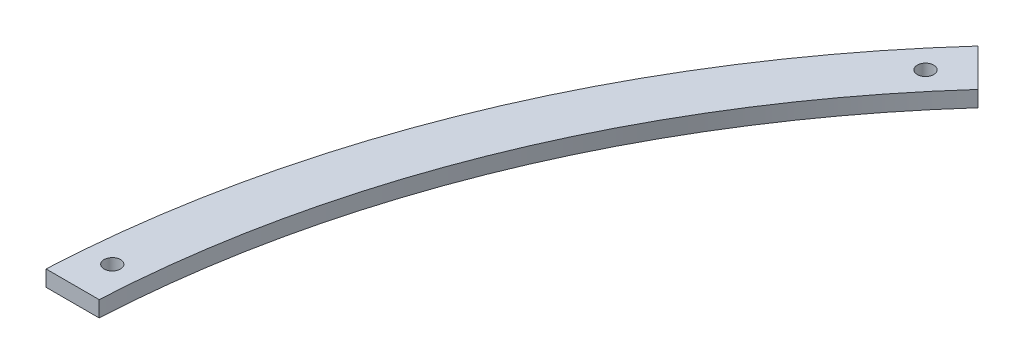
SolidWorks part; units mm, degrees
ref_plane "Front Plane" through (0, 0, 0) normal (0, 0, 1) x (1, 0, 0)
ref_plane "Top Plane" through (0, 0, 0) normal (0, 1, 0) x (1, 0, 0)
ref_plane "Right Plane" through (0, 0, 0) normal (1, 0, 0) x (0, 0, -1)
sketch "Sketch1" plane through (0, 0, 0) normal (0, 1, 0) x (1, 0, 0)
  line L1 (0, 200) -> (0, -200) construction
  line L6 (-200, 0) -> (200, 0) construction
  line L7 (-10, 199.7498) -> (-10, -199.7498) construction
  line L12 (-10, 199.7498) -> (-10, 189.7367)
  line L13 (-199.7498, 10) -> (199.7498, 10) construction
  line L14 (-199.7498, 10) -> (-189.7367, 10)
  line L15 (-141.4214, 141.4214) -> (141.4214, -141.4214) construction
  line L16 (-148.3155, 134.1734) -> (134.1734, -148.3155)
  arc A3 (-10, 199.7498) -> (-199.7498, 10) centre (0, 0) ccw
  arc A4 (-10, 189.7367) -> (-189.7367, 10) centre (0, 0) ccw
  arc A5 (-190, 0) -> (-189.7367, 10) centre (0, 0) ccw construction
  arc A6 (-200, 0) -> (-199.7498, 10) centre (0, 0) ccw construction
  circle A7 centre (0, 0) radius 195 construction
  dimension "D1" = 190
  dimension "D2" = 200
  dimension "D4" = 10
  dimension "D5" = 5
  dimension "D3" = 10
  dimension "D6" = 10
sketch "Sketch14" [suppressed] plane through (0, 0, 0) normal (0, 1, 0) x (1, 0, 0)
  line L0 (-200, 10) -> (200, 10) construction
  line L1 (-10, 200) -> (-10, -200) construction
  line L2 (-200, 10) -> (-189.7367, 10)
  line L3 (-10, 200) -> (-10, 189.7367)
  circle A0 centre (0, 0) radius 200 construction
  circle A1 centre (0, 0) radius 190 construction
  arc A2 (-10, 199.7498) -> (-199.7498, 10) centre (0, 0) ccw
  arc A3 (-10, 189.7367) -> (-189.7367, 10) centre (0, 0) ccw
sketch "roll" plane through (0, 0, 0) normal (0, 1, 0) x (1, 0, 0)
  line L0 (0, -195) -> (0, 195) construction
  dimension "D1" = 390
ref_axis "Axis1" through (0, -148.0362, 0) along (0, 1, 0)
extrude "base" add sketch "Sketch1" along normal mid plane 3 contours A4 L15 A3 L14 region at (-176.7216, 0, -73.2005)
sketch "Sketch25" plane through (0, 1.5, 0) normal (0, 1, 0) x (1, 0, 0)
  line L0 (-200, 0) -> (200, 0) construction
  line L1 (0, 200) -> (0, -200) construction
  line L2 (-200, 0) -> (200, 0)
  line L3 (0, 200) -> (0, -200)
  line L4 (0, 0) -> (-194.258, 16.9954) construction
  line L6 (-141.4214, 141.4214) -> (141.4214, -141.4214) construction
  line L7 (-141.4214, 141.4214) -> (141.4214, -141.4214)
  line L8 (0, 0) -> (-149.3787, 125.3436) construction
  circle A0 centre (0, 0) radius 195 construction
  circle A1 centre (0, 0) radius 195 construction
  dimension "D1" = 5
  dimension "D3" = 5
ref_plane "Plane1" through (0, 0, 0) normal (0.7071, 0, -0.7071) x (0.7071, 0, 0.7071)
hole_wizard "Ø3.1 (3.1) Diameter Hole1" positions "Sketch28" profile "Sketch29" hole size "Ø3.1" standard "ISO" end condition through all
sketch "Sketch28" plane through (0, 1.5, 0) normal (0, 1, 0) x (1, 0, 0)
  point P0 (-194.258, 16.9954)
  point P3 (-149.3787, 125.3436)
sketch "Sketch29" plane through (-194.258, 1.5, -16.9954) normal (1, 0, 0) x (0, 0, 1)
  line L0 (0, 0) -> (0, 3)
  line L1 (0, 3) -> (1.55, 3)
  line L2 (1.55, 3) -> (1.55, 0)
  line L5 (1.55, 0) -> (0, 0)
  line L11 (0, -6.35) -> (0, 107.95) construction
  dimension "Thru Hole Dia." = 3.1
  dimension "Thru Hole Depth" = 3
